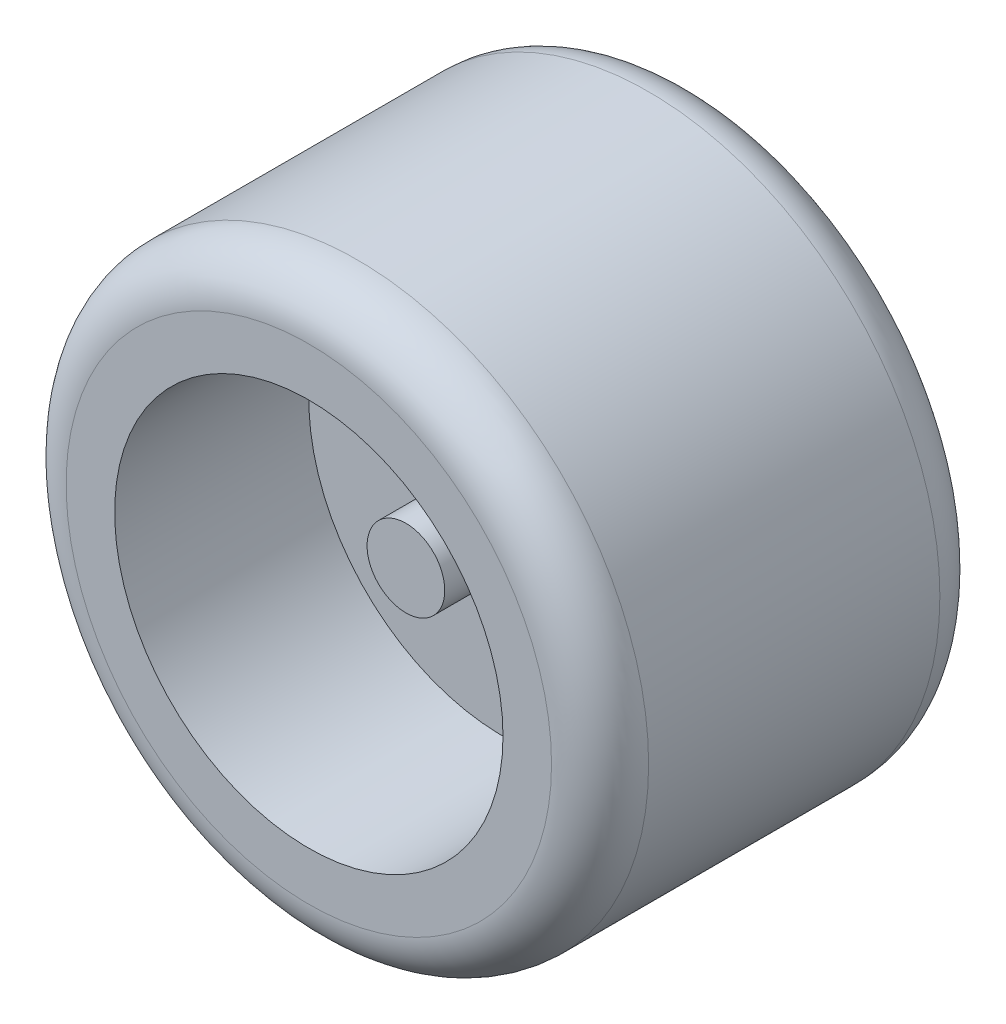
SolidWorks part; units mm, degrees
ref_plane "Front Plane" through (0, 0, 0) normal (0, 0, 1) x (1, 0, 0)
ref_plane "Top Plane" through (0, 0, 0) normal (0, 1, 0) x (1, 0, 0)
ref_plane "Right Plane" through (0, 0, 0) normal (1, 0, 0) x (0, 0, -1)
sketch "Sketch1" plane through (0, 0, 0) normal (0, 0, 1) x (1, 0, 0)
  circle A0 centre (0, 0) radius 15
  dimension "D1" = 30
extrude "Boss-Extrude1" add sketch "Sketch1" along normal blind 20 contours A0
sketch "Sketch2" plane through (0, 0, 20) normal (0, 0, 1) x (1, 0, 0)
  circle A0 centre (0, 0) radius 10
  dimension "D1" = 20
extrude "Cut-Extrude1" cut sketch "Sketch2" against normal blind 10
sketch "Sketch3" plane through (0, 0, 0) normal (0, 0, -1) x (-1, 0, 0)
  circle A0 centre (0, 0) radius 10
  dimension "D1" = 20
extrude "Cut-Extrude3" cut sketch "Sketch3" against normal blind 2
sketch "Sketch4" plane through (0, 0, 10) normal (0, 0, 1) x (1, 0, 0)
  circle A0 centre (0, 0) radius 2
  dimension "D1" = 4
extrude "Boss-Extrude2" add sketch "Sketch4" along normal blind 5
sketch "Sketch5" plane through (0, 0, 2) normal (0, 0, -1) x (-1, 0, 0)
  circle A0 centre (0, 0) radius 2
  dimension "D1" = 4
extrude "Boss-Extrude3" add sketch "Sketch5" along normal blind 2
fillet "Fillet2" radius 2.5 1 edges at (15, 0, 20)
fillet "Fillet3" radius 2.5 1 edges at (15, 0, 0)
ref_axis "Axis1" through (0, 0, 17.5) along (0, 0, -1)
